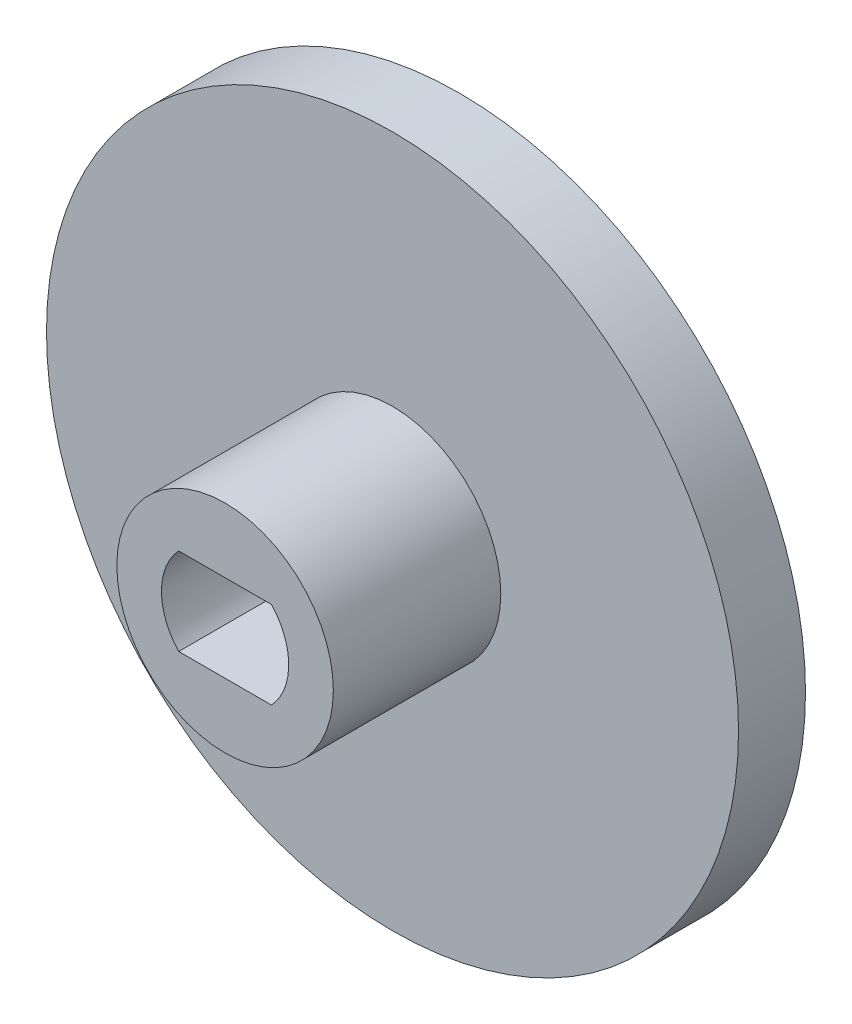
SolidWorks part; units mm, degrees
ref_plane "Front Plane" through (0, 0, 0) normal (0, 0, 1) x (1, 0, 0)
ref_plane "Top Plane" through (0, 0, 0) normal (0, 1, 0) x (1, 0, 0)
ref_plane "Right Plane" through (0, 0, 0) normal (1, 0, 0) x (0, 0, -1)
sketch "Sketch1" plane through (0, 0, 0) normal (0, 0, 1) x (1, 0, 0)
  circle A0 centre (0, 0) radius 15.5 construction
  circle A1 centre (0, 0) radius 15.5
extrude "Boss-Extrude1" add sketch "Sketch1" along normal blind 3
sketch "Sketch2" plane through (0, 0, 0) normal (0, 0, -1) x (-1, 0, 0)
  line L0 (-7.8174, 8.129) -> (-3.5527, 4.927)
  line L1 (0.2749, 6.0681) -> (2.0901, 11.0826)
  line L2 (-7.8774, 8.0491) -> (-3.6127, 4.8471)
  line L3 (0.3689, 6.0341) -> (2.1842, 11.0485)
  line L4 (-7.8774, 8.0491) -> (-3.6127, 4.8471) construction
  line L5 (0.3689, 6.0341) -> (2.1842, 11.0485) construction
  arc A0 (1.3416, 12.2836) -> (-7.8486, 9.5439) centre (0, 0) ccw
  arc A1 (-7.8486, 9.5439) -> (-7.8174, 8.129) centre (-7.277, 8.8488) ccw
  arc A2 (-3.5527, 4.927) -> (-2.5887, 4.8527) centre (-3.0123, 5.6468) ccw
  arc A3 (-0.491, 5.478) -> (-2.5887, 4.8527) centre (0, 0) ccw
  arc A4 (-0.491, 5.478) -> (0.2749, 6.0681) centre (-0.5714, 6.3744) ccw
  arc A5 (2.0901, 11.0826) -> (1.3416, 12.2836) centre (1.2439, 11.3889) ccw
  arc A6 (1.3524, 12.383) -> (-7.9122, 9.6211) centre (0, 0) ccw
  arc A7 (-7.9122, 9.6211) -> (-7.8774, 8.0491) centre (-7.277, 8.8488) ccw
  arc A8 (-3.6127, 4.8471) -> (-2.5416, 4.7645) centre (-3.0123, 5.6468) ccw
  arc A9 (-0.4821, 5.3784) -> (-2.5416, 4.7645) centre (0, 0) ccw
  arc A10 (-0.4821, 5.3784) -> (0.3689, 6.0341) centre (-0.5714, 6.3744) ccw
  arc A11 (2.1842, 11.0485) -> (1.3524, 12.383) centre (1.2439, 11.3889) ccw
  arc A12 (1.3524, 12.383) -> (-7.9122, 9.6211) centre (0, 0) ccw construction
  arc A13 (-7.9122, 9.6211) -> (-7.8774, 8.0491) centre (-7.277, 8.8488) ccw construction
  arc A14 (-3.6127, 4.8471) -> (-2.5416, 4.7645) centre (-3.0123, 5.6468) ccw construction
  arc A15 (-0.4821, 5.3784) -> (-2.5416, 4.7645) centre (0, 0) ccw construction
  arc A16 (-0.4821, 5.3784) -> (0.3689, 6.0341) centre (-0.5714, 6.3744) ccw construction
  arc A17 (2.1842, 11.0485) -> (1.3524, 12.383) centre (1.2439, 11.3889) ccw construction
  dimension "D1" = 0
  dimension "D2" = 0.1
extrude "Boss-Extrude2" add sketch "Sketch2" along normal offset from surface (1.9 mm away) 0.3
pattern_circular "CirPattern1" count 5 over 360 about axis through (0, 0, 3) along (0, 0, -1) of "Boss-Extrude2"
sketch "Sketch3" plane through (0, 0, 3) normal (0, 0, 1) x (1, 0, 0)
  circle A0 centre (0, 0) radius 4.85
  dimension "D1" = 9.7
extrude "Boss-Extrude3" add sketch "Sketch3" along normal blind 7.5
sketch "Sketch4" plane through (0, 0, 0) normal (0, 0, 1) x (1, 0, 0)
  circle A0 centre (0, 0) radius 2
  dimension "D1" = 4
extrude "Cut-Extrude1" cut sketch "Sketch4" along normal offset from surface (3 mm away) 7.5 up to face at (4.85, 0, 10.5)
sketch "Sketch5" plane through (0, 0, 10.5) normal (0, 0, 1) x (1, 0, 0)
  line L0 (-2.0785, 1.95) -> (2.0785, 1.95)
  line L1 (2.0785, -1.95) -> (-2.0785, -1.95)
  arc A0 (-2.0785, 1.95) -> (-2.0785, -1.95) centre (0, 0) ccw
  arc A1 (2.0785, -1.95) -> (2.0785, 1.95) centre (0, 0) ccw
  dimension "D1" = 5.7
  dimension "D2" = 3.9
extrude "Cut-Extrude2" cut sketch "Sketch5" against normal up to surface (7.5 mm away) up to face at (2, 0, 3)
sketch "Sketch6" plane through (0, 0, 0) normal (0, 0, -1) x (-1, 0, 0)
  circle A1 centre (0, 0) radius 15.5 construction
  circle A2 centre (0, 0) radius 15.5
  circle A3 centre (0, 0) radius 13.5
  dimension "D1" = 2
extrude "Boss-Extrude4" [suppressed] add sketch "Sketch6" along normal offset from surface (0.9 mm away) 0.1
